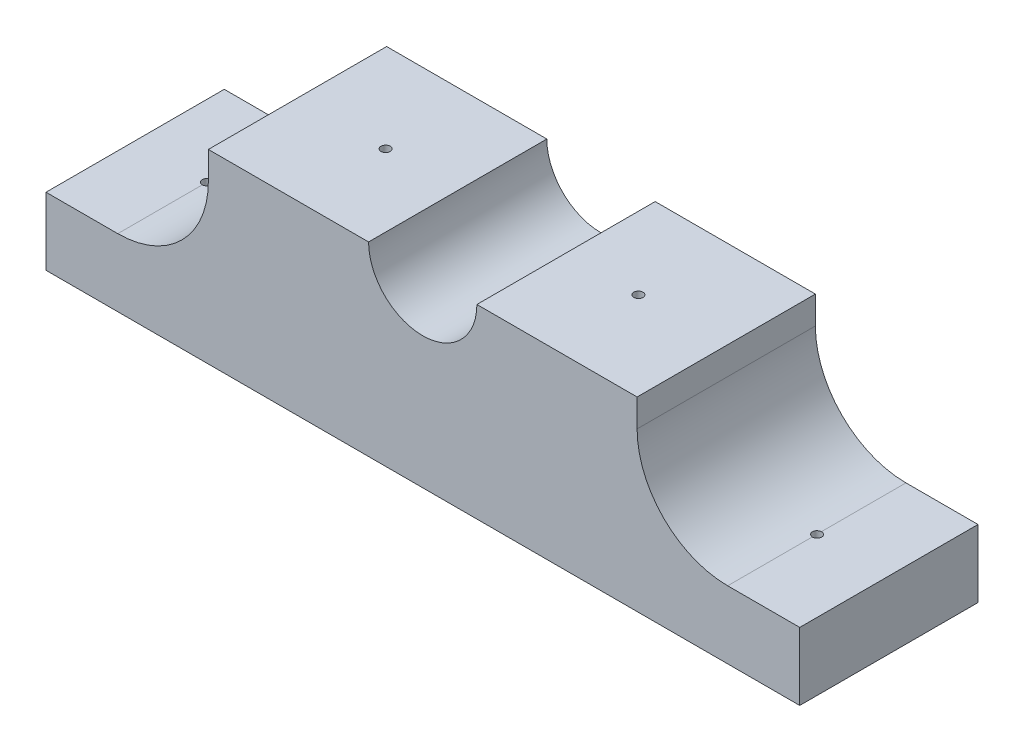
SolidWorks part; units mm, degrees
material "Custom Plastic"
ref_plane "Front Plane" through (0, 0, 0) normal (0, 0, 1) x (1, 0, 0)
ref_plane "Top Plane" through (0, 0, 0) normal (0, 1, 0) x (1, 0, 0)
ref_plane "Right Plane" through (0, 0, 0) normal (1, 0, 0) x (0, 0, -1)
sketch "Sketch2" plane through (0, 0, 0) normal (0, 1, 0) x (1, 0, 0)
  line L1 (-20.873, -4.9365) -> (20.873, -4.9365)
  line L2 (-20.873, -4.9365) -> (-20.873, 4.9365)
  line L3 (-20.873, 4.9365) -> (20.873, 4.9365)
  line L4 (20.873, -4.9365) -> (20.873, 4.9365)
  line L5 (-20.873, -4.9365) -> (20.873, 4.9365) construction
  line L6 (-20.873, 4.9365) -> (20.873, -4.9365) construction
  point P0 (0, 0)
  dimension "D1" = 41.746
  dimension "D2" = 9.873
extrude "Boss-Extrude1" add sketch "Sketch2" along normal blind 3.746 contours L1 L4 L3 L2
sketch "Sketch3" plane through (0, 3.746, 0) normal (0, 1, 0) x (1, 0, 0)
  line L0 (-11.8803, 4.9365) -> (-11.8803, -4.9365)
  line L1 (-20.873, 4.9365) -> (20.873, 4.9365) construction
  line L2 (-11.8803, 4.9365) -> (11.8657, 4.9365)
  line L3 (-20.873, -4.9365) -> (20.873, -4.9365) construction
  line L4 (-11.8803, -4.9365) -> (11.8657, -4.9365)
  line L5 (11.8657, -4.9365) -> (11.8657, 4.9365)
extrude "Boss-Extrude2" add sketch "Sketch3" along normal blind 6.5485
fillet "Fillet1" radius 5.0165 2 edges at (11.8657, 3.746, 0) (-11.8803, 3.746, 0)
sketch "Sketch4" plane through (0, 0, 4.9365) normal (0, 0, 1) x (1, 0, 0)
  line L0 (-11.8803, 10.2945) -> (11.8657, 10.2945) construction
  circle A0 centre (-0.0073, 10.2945) radius 2.9997
extrude "Cut-Extrude1" cut sketch "Sketch4" against normal through all
sketch "Sketch5" plane through (0, 10.2945, 0) normal (0, 1, 0) x (1, 0, 0)
  line L0 (-11.8803, 4.9365) -> (11.8657, 4.9365)
  line L1 (11.8657, 4.9365) -> (11.8657, -4.9365)
  line L2 (11.8657, -4.9365) -> (-11.8803, -4.9365)
  line L3 (-16.8968, -4.9365) -> (-11.8803, -4.9365) construction
  line L4 (-11.8803, -4.9365) -> (-3.0071, -4.9365) construction
  line L5 (-11.8803, -4.9365) -> (-11.8803, 4.9365)
sketch "Sketch6" plane through (0, 3.746, 0) normal (0, 1, 0) x (1, 0, 0)
  line L2 (-16.8968, -4.9365) -> (-16.8968, 4.9365) construction
  circle A0 centre (-16.8968, 0) radius 0.254
  circle A1 centre (16.8968, 0) radius 0.254
extrude "Cut-Extrude2" cut sketch "Sketch6" against normal blind 2.54 and the other way through all
sketch "Sketch7" plane through (0, 10.2945, 0) normal (0, 1, 0) x (1, 0, 0)
  circle A0 centre (-7, 0) radius 0.254
  circle A1 centre (7, 0) radius 0.254
  point P7 (0, 0)
extrude "Cut-Extrude3" cut sketch "Sketch7" against normal blind 2.54
